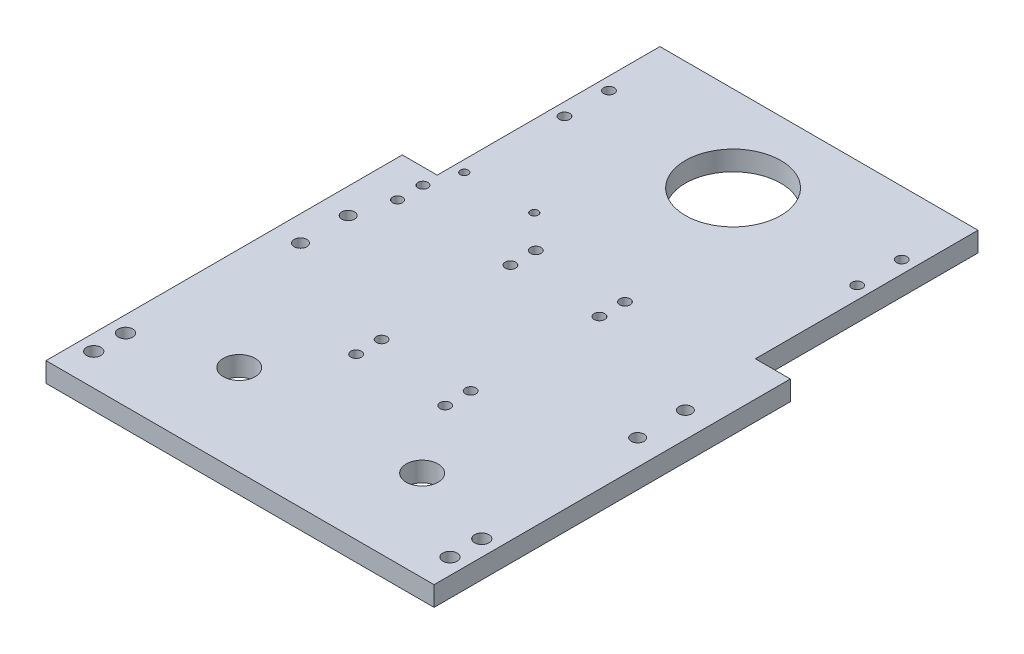
SolidWorks part; units mm, degrees
ref_plane "Front Plane" through (0, 0, 0) normal (0, 0, 1) x (1, 0, 0)
ref_plane "Top Plane" through (0, 0, 0) normal (0, 1, 0) x (1, 0, 0)
ref_plane "Right Plane" through (0, 0, 0) normal (1, 0, 0) x (0, 0, -1)
sketch "Sketch1" plane through (0, 0, 0) normal (0, 1, 0) x (1, 0, 0)
  line L1 (-61, 56) -> (61, 56)
  line L2 (-61, 56) -> (-61, -56)
  line L3 (-61, -56) -> (61, -56)
  line L4 (61, 56) -> (61, -56)
  line L5 (-61, 56) -> (61, -56) construction
  line L6 (-61, -56) -> (61, 56) construction
  point P0 (0, 0)
  dimension "D1" = 122
  dimension "D2" = 112
extrude "Boss-Extrude1" add sketch "Sketch1" along normal blind 6.2
sketch "Sketch2" plane through (0, 0, 0) normal (0, 1, 0) x (1, 0, 0)
  line L0 (61, 56) -> (-61, 56) construction
  line L1 (-50, 56) -> (50, 56)
  line L2 (-50, 56) -> (-50, 126)
  line L3 (-50, 126) -> (50, 126)
  line L4 (50, 56) -> (50, 126)
  line L5 (0, -3.41) -> (0, 3.41) construction
  dimension "D1" = 100
  dimension "D2" = 50
  dimension "D3" = 70
extrude "Boss-Extrude2" add sketch "Sketch2" along normal blind 6.2
sketch "Sketch3" plane through (0, 6.2, 0) normal (0, 1, 0) x (1, 0, 0)
  line L0 (-50, 56) -> (50, 56) construction
  line L1 (-50, 126) -> (-50, 56) construction
  line L3 (0, -3.41) -> (0, 3.41) construction
  line L4 (0, 126) -> (0, 56) construction
  line L5 (50, 126) -> (-50, 126) construction
  line L6 (0, 99) -> (50, 99) construction
  line L7 (50, 56) -> (50, 126) construction
  circle A0 centre (-46.5, 61) radius 1.25
  circle A1 centre (-24.5, 61) radius 1.25
  circle A3 centre (-46.013, 106) radius 1.65
  circle A6 centre (0, 99) radius 15
  circle A7 centre (-46.013, 92) radius 1.65
  circle A8 centre (46.013, 92) radius 1.65
  circle A9 centre (46.013, 106) radius 1.65
  dimension "D1" = 2.5
  dimension "D2" = 2.5
  dimension "D16" = 3.3
  dimension "D17" = 30
  dimension "D3" = 5
  dimension "D4" = 5
  dimension "D5" = 22
  dimension "D6" = 3.5
  dimension "D18" = 43
  dimension "D7" = 46.013
  dimension "D8" = 7
extrude "Cut-Extrude1" cut sketch "Sketch3" against normal through all
sketch "Sketch4" plane through (0, 6.2, 0) normal (0, 1, 0) x (1, 0, 0)
  line L0 (-46.5, 61) -> (-24.5, 61) construction
  line L1 (-35.5, 61) -> (-35.5, 13.896) construction
  line L2 (-50, 56) -> (-61, 56) construction
  line L3 (61, 56) -> (50, 56) construction
  line L4 (0, -3.41) -> (0, 3.41) construction
  line L5 (-15.5456, 22.75) -> (18.1861, 22.75) construction
  circle A0 centre (-49.5, 51) radius 1.55
  circle A1 centre (-21.5, 51) radius 1.55 construction
  circle A2 centre (-21.5, 43) radius 1.55 construction
  circle A3 centre (-49.5, 43) radius 1.55
  circle A4 centre (-14, 2.5) radius 1.65
  circle A5 centre (14, 2.5) radius 1.65
  circle A6 centre (14, -5.5) radius 1.65
  circle A7 centre (-14, -5.5) radius 1.65
  circle A8 centre (-14, 51) radius 1.65
  circle A9 centre (14, 51) radius 1.65
  circle A10 centre (14, 43) radius 1.65
  circle A11 centre (-14, 43) radius 1.65
  dimension "D1" = 3.1
  dimension "D8" = 3.3
  dimension "D9" = 14
  dimension "D2" = 5
  dimension "D5" = 53.5
  dimension "D10" = 14
  dimension "D11" = 20.25
  dimension "D3" = 2
  dimension "D4" = 2
  dimension "D6" = 2
  dimension "D7" = 2
extrude "Cut-Extrude2" cut sketch "Sketch4" against normal through all
sketch "Sketch5" plane through (0, 6.2, 0) normal (0, 1, 0) x (1, 0, 0)
  line L0 (-61, 56) -> (-61, -56) construction
  line L1 (-50, 56) -> (-61, 56) construction
  line L2 (0, -3.41) -> (0, 3.41) construction
  circle A0 centre (-53, 31) radius 2
  circle A1 centre (-53, 16) radius 2
  circle A2 centre (53, 16) radius 2
  circle A3 centre (53, 31) radius 2
  dimension "D3" = 4
  dimension "D4" = 4
  dimension "D1" = 8
  dimension "D2" = 8
  dimension "D5" = 15
  dimension "D6" = 25
extrude "Cut-Extrude3" cut sketch "Sketch5" against normal blind 10
sketch "Sketch6" plane through (0, 6.2, 0) normal (0, 1, 0) x (1, 0, 0)
  line L0 (0, 55.945) -> (0, -50.7895) construction
  line L1 (0, -3.41) -> (0, 3.41) construction
  line L2 (-28.75, -27.5) -> (28.75, -27.5) construction
  line L3 (61, 56) -> (50, 56) construction
  circle A0 centre (-28.75, -27.5) radius 5
  circle A1 centre (28.75, -27.5) radius 5
  dimension "D4" = 10
  dimension "D5" = 10
  dimension "D1" = 83.5
  dimension "D2" = 28.75
  dimension "D3" = 28.75
extrude "Cut-Extrude4" cut sketch "Sketch6" against normal blind 10
sketch "Sketch7" plane through (0, 6.2, 0) normal (0, 1, 0) x (1, 0, 0)
  line L0 (-61, 56) -> (-61, -56) construction
  line L1 (-61, -56) -> (61, -56) construction
  line L2 (0, -3.41) -> (0, 3.41) construction
  circle A0 centre (-56, -36) radius 2.25
  circle A1 centre (-56, -46) radius 2.25
  circle A2 centre (56, -46) radius 2.25
  circle A3 centre (56, -36) radius 2.25
  dimension "D5" = 4.5
  dimension "D6" = 4.5
  dimension "D1" = 5
  dimension "D3" = 10
  dimension "D4" = 10
extrude "Cut-Extrude5" cut sketch "Sketch7" against normal through all
equation "\"D2@Sketch2\"=\"D1@Sketch2\"/2"
equation "\"D2@Sketch3\"=\"D1@Sketch3\""
equation "\"D4@Sketch3\"=\"D3@Sketch3\""
equation "\"D6@Sketch7\"=\"D5@Sketch7\""
